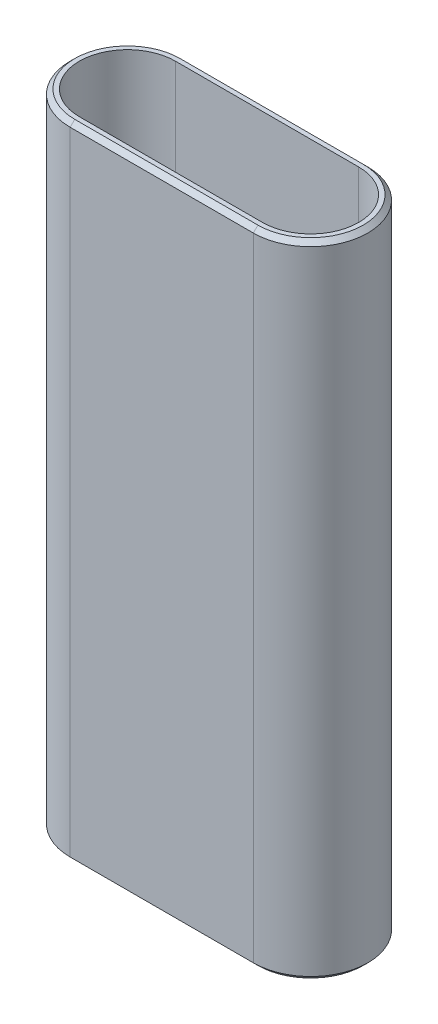
SolidWorks part; units mm, degrees
ref_plane "Front Plane" through (0, 0, 0) normal (0, 0, 1) x (1, 0, 0)
ref_plane "Top Plane" through (0, 0, 0) normal (0, 1, 0) x (1, 0, 0)
ref_plane "Right Plane" through (0, 0, 0) normal (1, 0, 0) x (0, 0, -1)
sketch "Sketch2" plane through (0, 12, 0) normal (0, -1, 0) x (1, 0, 0)
  line L8 (5.45, 3.45) -> (5.45, -3.45) construction
  line L9 (-7.45, -5.65) -> (7.45, -5.65)
  line L10 (-7.45, -5.65) -> (-7.45, 5.65)
  line L11 (-7.45, 5.65) -> (7.45, 5.65)
  line L12 (4.15, -3.65) -> (4.15, 3.65)
  line L13 (4.15, 3.65) -> (-4.15, 3.65)
  line L14 (-4.15, 3.65) -> (-4.15, -3.65)
  line L15 (-4.15, -3.65) -> (4.15, -3.65)
  line L16 (4.15, -3.65) -> (4.15, 3.65)
  line L17 (4.15, 3.65) -> (-4.15, 3.65)
  line L18 (-4.15, 3.65) -> (-4.15, -3.65)
  line L19 (-4.15, -3.65) -> (4.15, -3.65)
  line L20 (7.45, -5.65) -> (7.45, 5.65)
  line L21 (0, 5.65) -> (0, -5.65) construction
  line L22 (-7.45, 0) -> (7.45, 0) construction
  point P0 (0, 0)
  dimension "D2" = 2
  dimension "D3" = 2
  dimension "D4" = 8.3
  dimension "D5" = 7.3
  dimension "D1" = 0.2
extrude "Boss-Extrude1" add sketch "Sketch2" along normal offset from surface (12.6 mm away) 0.6 offset beyond the face yes
sketch "Sketch4" plane through (0, 0, 0) normal (1, 0, 0) x (0, 0, -1)
  line L1 (-1.6, 9.8) -> (-1.6, 8) construction
  line L2 (1.6, 8) -> (1.6, 9.8) construction
  line L3 (2.75, 8) -> (1.6, 8) construction
  line L4 (-1.6, 8) -> (-2.75, 8) construction
  line L5 (-2.75, 8) -> (-2.75, 12) construction
  line L6 (-2.75, 12) -> (-3.45, 12) construction
  line L7 (-3.45, 12) -> (-3.45, 0) construction
  line L8 (-3.45, 0) -> (3.45, 0) construction
  line L9 (3.45, 0) -> (3.45, 12) construction
  line L10 (3.45, 12) -> (2.75, 12) construction
  line L11 (2.75, 12) -> (2.75, 8) construction
  line L13 (-1.6, 9.8) -> (-1.6, 8) construction
  line L14 (1.6, 8) -> (1.6, 9.8) construction
  line L15 (2.75, 8) -> (1.6, 8) construction
  line L16 (-1.6, 8) -> (-2.75, 8) construction
  line L17 (-2.75, 8) -> (-2.75, 12) construction
  line L18 (-2.75, 12) -> (-3.45, 12) construction
  line L19 (-3.45, 12) -> (-3.45, 0) construction
  line L20 (-3.45, 0) -> (3.45, 0) construction
  line L21 (3.45, 0) -> (3.45, 12) construction
  line L22 (3.45, 12) -> (2.75, 12) construction
  line L23 (2.75, 12) -> (2.75, 8) construction
  line L24 (0, -990) -> (0, 49010) construction
  line L25 (-2.3, 10.25) -> (2.3, 10.25)
  line L26 (-2.3, 10.25) -> (-2.3, 7)
  line L27 (-2.3, 7) -> (2.3, 7)
  line L28 (1.6, 10) -> (-1.6, 10)
  line L29 (-1.6, 10) -> (-1.6, 9.8)
  line L30 (-1.6, 9.8) -> (1.6, 9.8)
  line L31 (1.6, 9.8) -> (1.6, 10)
  line L32 (1.6, 10) -> (-1.6, 10) construction
  line L33 (-1.6, 10) -> (-1.6, 9.8) construction
  line L34 (2.3, 10.25) -> (2.3, 7)
  line L35 (1.6, 9.8) -> (1.6, 10) construction
  point P20 (0, 10)
  dimension "D2" = 0.7
  dimension "D3" = 0.5
  dimension "D4" = 1
  dimension "D1" = 0
extrude "Cut-Extrude1" cut sketch "Sketch4" against normal through all both and the other way through all
sketch "Sketch5" plane through (0, -0.6, 0) normal (0, -1, 0) x (1, 0, 0)
  line L0 (-20, 0) -> (20, 0) construction
  line L1 (-20, 12.5) -> (20, 12.5)
  line L2 (-20, -12.5) -> (20, -12.5)
  arc A0 (-20, 12.5) -> (-20, -12.5) centre (-20, 0) ccw
  arc A1 (20, -12.5) -> (20, 12.5) centre (20, 0) ccw
  point P2 (0, 0)
  dimension "D1" = 25
  dimension "D2" = 40
extrude "Boss-Extrude2" add sketch "Sketch5" along normal blind 3
sketch "Sketch7" plane through (0, -0.6, 0) normal (0, 1, 0) x (1, 0, 0)
  line L0 (-20, -10.5) -> (20, -10.5)
  line L1 (20, 10.5) -> (-20, 10.5)
  line L2 (-20, -12.5) -> (20, -12.5)
  line L3 (20, 12.5) -> (-20, 12.5)
  line L4 (-20, -12.5) -> (20, -12.5)
  line L5 (20, 12.5) -> (-20, 12.5)
  arc A0 (20, -10.5) -> (20, 10.5) centre (20, 0) ccw
  arc A1 (-20, 10.5) -> (-20, -10.5) centre (-20, 0) ccw
  arc A2 (-20, 12.5) -> (-20, -12.5) centre (-20, 0) ccw
  arc A3 (20, -12.5) -> (20, 12.5) centre (20, 0) ccw
  arc A4 (-20, 12.5) -> (-20, -12.5) centre (-20, 0) ccw
  arc A5 (20, -12.5) -> (20, 12.5) centre (20, 0) ccw
  dimension "D1" = 0
  dimension "D2" = 2
extrude "Boss-Extrude3" add sketch "Sketch7" along normal blind 137
chamfer "Chamfer1" distance 1 angle 45 8 edges at (32.5, -3.6, 0) (0, -3.6, 12.5) (0, -3.6, -12.5) (-32.5, -3.6, 0) (32.5, 136.4, 0) (0, 136.4, -12.5) (0, 136.4, 12.5) (-32.5, 136.4, 0)
chamfer "Chamfer2" distance 0.8 angle 45 8 edges at (-7.45, 12, 0) (0, 12, -5.65) (7.45, 12, 0) (0, 12, 5.65) (0, 12, 3.65) (4.15, 12, 0) (0, 12, -3.65) (-4.15, 12, 0)
chamfer "Chamfer3" distance 2 angle 45 4 edges at (-7.45, 5.3, 5.65) (-7.45, 5.3, -5.65) (7.45, 5.3, -5.65) (7.45, 5.3, 5.65)
equation "\"case_length\"= 140"
equation "\"plate_thickness\"= 3"
equation "\"D1@Boss-Extrude2\"=\"plate_thickness\""
equation "\"D1@Boss-Extrude3\"=\"case_length\"-\"plate_thickness\""
equation "\"case_height\"= 25"
equation "\"case_width\"= 65"
equation "\"case_to_shell_offset\"= 19.6"
equation "\"body_tip_distance\"= 30"
equation "\"D2@Sketch5\"=\"case_width\"-\"case_height\""
equation "\"D1@Sketch5\"=\"case_height\""
